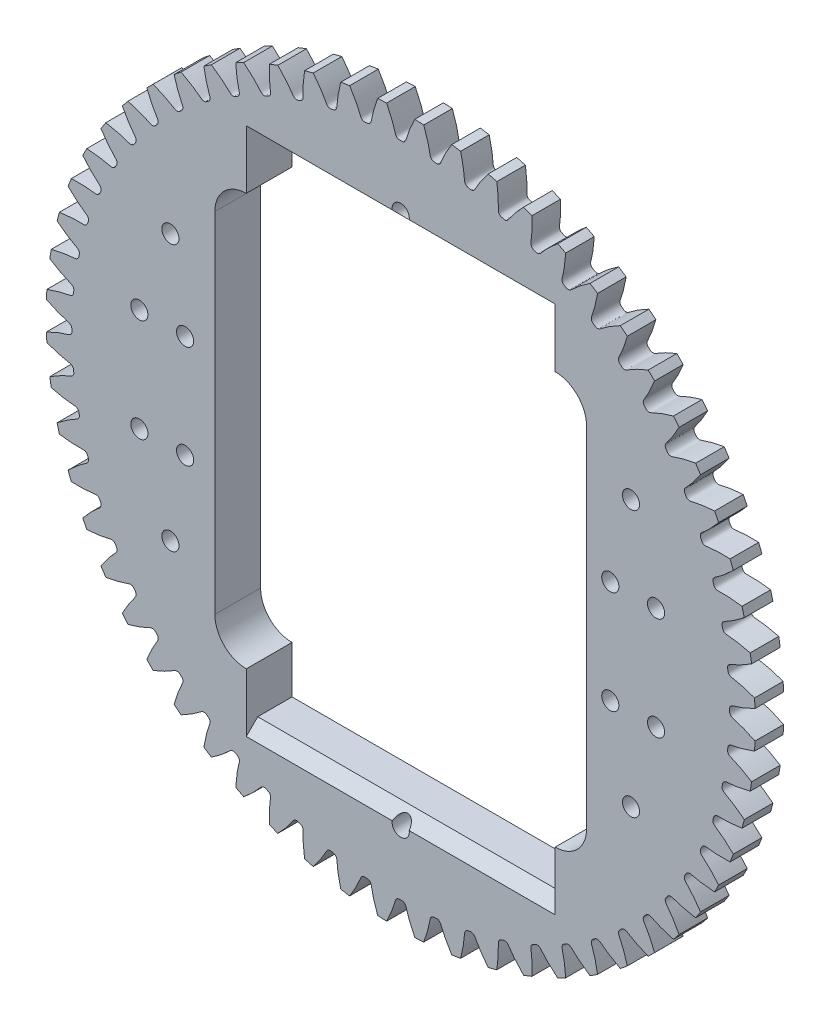
SolidWorks part; units mm, degrees
note: '?' marks a value the reader was unsure of.
material "6061 合金"
ref_plane "前视基准面" through (0, 0, 0) normal (0, 0, 1) x (1, 0, 0)
ref_plane "上视基准面" through (0, 0, 0) normal (0, 1, 0) x (1, 0, 0)
ref_plane "右视基准面" through (0, 0, 0) normal (1, 0, 0) x (0, 0, -1)
ref_axis "基准轴1" through (0, 0, 55) along (0, 0, -1)?
sketch "旋转草图大直齿轮" plane through (0, 0, 0) normal (1, 0, 0) x (0, 0, -1)
  line L0 (0, 0) -> (1, 0) construction
  line L1 (-2, 0) -> (-2, 62)
  line L2 (-2, 62) -> (3, 62)
  line L3 (3, 62) -> (3, 0)
  line L4 (3, 0) -> (-2, 0)
  dimension "D1" = 62
  dimension "D2" = 5
revolve "大直齿轮" add sketch "旋转草图大直齿轮" angle 360 about L0
sketch "齿草图大直齿轮" plane through (0, 0, 0) normal (0, 0, 1) x (1, 0, 0)
  arc A0 (62.0493, 2.5099) -> (62.0493, -2.5099) centre (0, 0) cw
  spline S0 degree 3 poles (62.0493, -2.5099) (61.8808, -2.4237) (61.6298, -2.2987) (61.2966, -2.1398) (61.055, -2.0279) (60.8186, -1.9215) (60.5875, -1.8206) (60.3617, -1.7251) (60.1414, -1.6347) (59.9267, -1.5495) (59.7175, -1.4691) (59.5142, -1.3936) (59.3166, -1.3227) (59.1248, -1.2563) (58.9391, -1.1943) (58.7593, -1.1364) (58.5856, -1.083) (58.3405, -1.0086) (58.1215, -0.9581) (57.9426, -0.8805) (57.8626, -0.8379) (57.7777, -0.7808) (57.6863, -0.6999) (57.5933, -0.5815) (57.52, -0.4205) (57.4921, -0.218) (57.5043, 0) (57.4921, 0.218) (57.52, 0.4205) (57.5933, 0.5815) (57.6863, 0.6999) (57.7777, 0.7808) (57.8626, 0.8379) (57.9426, 0.8805) (58.1215, 0.9581) (58.3405, 1.0086) (58.5856, 1.083) (58.7593, 1.1364) (58.9391, 1.1943) (59.1248, 1.2563) (59.3166, 1.3227) (59.5142, 1.3936) (59.7175, 1.4691) (59.9267, 1.5495) (60.1414, 1.6347) (60.3617, 1.7251) (60.5875, 1.8206) (60.8186, 1.9215) (61.055, 2.0279) (61.2966, 2.1398) (61.6298, 2.2987) (61.8808, 2.4237) (62.0493, 2.5099) knots 0 0 0 0 0.051766 0.076686 0.100963 0.124598 0.147592 0.169943 0.191651 0.212718 0.233143 0.252925 0.272065 0.290563 0.308419 0.325633 0.342204 0.358133 0.395729 0.403327 0.411415 0.420483 0.431261 0.444675 0.461387 0.478965 0.5 0.521035 0.538613 0.555325 0.568739 0.579517 0.588585 0.596673 0.604271 0.641867 0.657796 0.674367 0.691581 0.709437 0.727935 0.747075 0.766857 0.787282 0.808349 0.830057 0.852408 0.875402 0.899037 0.923314 0.948234 1 1 1 1
extrude "齿拉伸切除大直齿轮" cut sketch "齿草图大直齿轮" against normal blind 3 and the other way blind 3
pattern_circular "齿形大直齿轮" count 60 every 6 about axis through (0, 0, 55) along (0, 0, -1) of "齿拉伸切除大直齿轮"
sketch "孔旋转草图" plane through (0, 0, 0) normal (1, 0, 0) x (0, 0, -1)
  line L0 (0, 0) -> (1, 0) construction
  line L1 (-3, 0) -> (3, 0)
  line L2 (3, 0) -> (3, 5)
  line L3 (3, 5) -> (-3, 5)
  line L4 (-3, 5) -> (-3, 0)
  dimension "TaperSide1" = 5
  dimension "TaperSide2" = 5
revolve "孔旋转切除" cut sketch "孔旋转草图" angle 360 about L0
sketch "辅助草图大直齿轮" plane through (0, 0, 0) normal (0, 0, 1) x (1, 0, 0)
  circle A0 centre (0, 0) radius 60 construction
  circle A1 centre (0, 0) radius 56.3816 construction
  circle A2 centre (0, 0) radius 58.183 construction
  circle A3 centre (0, 0) radius 62 construction
  circle A4 centre (0, 0) radius 57.5 construction
  dimension "PitchDiameter" = 120
  dimension "BaseDiameter" = 112.7631
  dimension "FormDiameter" = 116.366
  dimension "MajorDiameter" = 124
  dimension "MinorDiameter" = 115
sketch "草图17" plane through (0, 0, -3) normal (0, 0, -1) x (-1, 0, 0)
  circle A0 centre (0, 0) radius 52.5
  dimension "D1" = 105
extrude "凸台-拉伸1" add sketch "草图17" along normal blind 3
sketch "草图5" plane through (0, 0, 2) normal (0, 0, 1) x (1, 0, 0)
  line L1 (-27, -44.25) -> (27, -44.25)
  line L2 (-27, -44.25) -> (-27, 44.25)
  line L3 (-27, 44.25) -> (27, 44.25)
  line L4 (27, -44.25) -> (27, 44.25)
  line L5 (-27, -44.25) -> (27, 44.25) construction
  line L6 (-27, 44.25) -> (27, -44.25) construction
  point P0 (0, 0)
  dimension "D1" = 88.5
  dimension "D2" = 54
extrude "切除-拉伸2" cut sketch "草图5" against normal through all
sketch "草图6" plane through (0, 0, 2) normal (0, 0, 1) x (1, 0, 0)
  line L0 (27, -44.25) -> (27, 44.25) construction
  line L1 (25.5, -36) -> (28.5, -36)
  line L2 (25.5, -36) -> (25.5, 36)
  line L3 (25.5, 36) -> (28.5, 36)
  line L4 (28.5, -36) -> (28.5, 36)
  line L5 (25.5, -36) -> (28.5, 36) construction
  line L6 (25.5, 36) -> (28.5, -36) construction
  line L7 (-27, 44.25) -> (-27, -44.25) construction
  line L8 (-30.2, -30) -> (-23.8, -30)
  line L9 (-30.2, -30) -> (-30.2, 30)
  line L10 (-30.2, 30) -> (-23.8, 30)
  line L11 (-23.8, -30) -> (-23.8, 30)
  line L12 (-30.2, -30) -> (-23.8, 30) construction
  line L13 (-30.2, 30) -> (-23.8, -30) construction
  point P0 (27, 0)
  point P7 (-27, 0)
  dimension "D1" = 72
  dimension "D2" = 3
  dimension "D3" = 60
  dimension "D4" = 6.4
chamfer "倒角3" distance 2 angle 45 2 edges at (0, -44.25, 2) (0, 44.25, 2)
sketch "草图9" plane through (0, 0, 2) normal (0, 0, 1) x (1, 0, 0)
  circle A0 centre (0, 0) radius 46.5 construction
  circle A1 centre (0, 46.5) radius 1.5
  circle A2 centre (40.2702, 23.25) radius 1.5
  circle A3 centre (40.2702, -23.25) radius 1.5
  circle A4 centre (0, -46.5) radius 1.5
  circle A5 centre (-40.2702, -23.25) radius 1.5
  circle A6 centre (-40.2702, 23.25) radius 1.5
  point P19 (0, 0)
  dimension "D1" = 93
  dimension "D2" = 3
  dimension "D3" = 6
extrude "切除-拉伸4" cut sketch "草图9" against normal through all
cosmetic thread "装饰螺纹线9" parameters "D2"=4
cosmetic thread "装饰螺纹线10" parameters "D2"=4
sketch "草图12" plane through (0, 0, 2) normal (0, 0, 1) x (1, 0, 0)
  line L2 (-32.5, -36) -> (32.5, -36)
  line L3 (-32.5, -36) -> (-32.5, 36)
  line L4 (-32.5, 36) -> (32.5, 36)
  line L5 (32.5, -36) -> (32.5, 36)
  line L6 (-32.5, -36) -> (32.5, 36) construction
  line L7 (-32.5, 36) -> (32.5, -36) construction
  point P2 (0, 0)
  dimension "D1" = 72
  dimension "D2" = 65
extrude "切除-拉伸5" cut sketch "草图12" against normal through all
fillet "圆角1" radius 5.5 4 edges at (-32.5, 36, -2) (32.5, -36, -2) (32.5, 36, -2) (-32.5, -36, -2)
extrude "切除-拉伸6" [suppressed] cut sketch "草图13" against normal blind 20
sketch "草图13" plane through (-180.0509, -122.298, 3) normal (0, 0, 1) x (0.0478, -0.9989, 0)
  circle A8 centre (-97.7427, 141.8774) radius 1.5
  circle A9 centre (-101.8613, 148.7357) radius 1.5
  circle A10 centre (-82.3114, 151.1443) radius 1.5
  circle A11 centre (-86.4301, 158.0026) radius 1.5
  circle A12 centre (-140.0617, 212.3469) radius 1.5
  circle A13 centre (-144.1803, 219.2052) radius 1.5
  circle A14 centre (-124.6304, 221.6138) radius 1.5
  circle A15 centre (-128.749, 228.4721) radius 1.5
extrude "切除-拉伸7" cut sketch "草图18" against normal blind 20
sketch "草图18" plane through (90.5739, -197.9567, 2) normal (0, 0, 1) x (0.9919, -0.1274, 0)
  circle A8 centre (-161.5296, 187.9091) radius 1.5
  circle A9 centre (-153.5947, 188.9283) radius 1.5
  circle A10 centre (-159.2364, 170.0558) radius 1.5
  circle A11 centre (-151.3016, 171.075) radius 1.5
  circle A12 centre (-79.8506, 198.4004) radius 1.5
  circle A13 centre (-71.9158, 199.4196) radius 1.5
  circle A14 centre (-77.5574, 180.5471) radius 1.5
  circle A15 centre (-69.6226, 181.5663) radius 1.5
